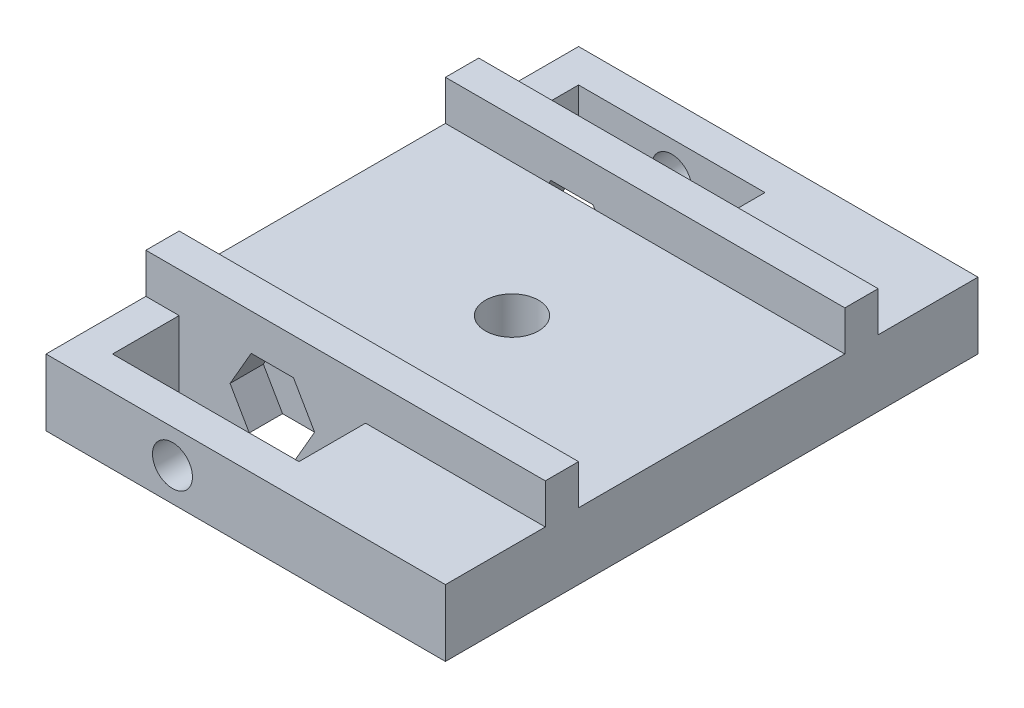
SolidWorks part; units mm, degrees
note: The reader was unsure of these and kept them because the rebuilt part matched: shared geometry of "Sketch1<3>", "Sketch4<3>".
ref_plane "Front" through (0, 0, 0) normal (0, 0, 1) x (1, 0, 0)
ref_plane "Top" through (0, 0, 0) normal (0, 1, 0) x (1, 0, 0)
ref_plane "Right" through (0, 0, 0) normal (1, 0, 0) x (0, 0, -1)
sketch "Sketch1" plane through (0, 0, 0) normal (0, 1, 0) x (1, 0, 0)
  line L0 (0, -20) -> (0, -22.5)
  line L1 (0, 0) -> (-30, 0)
  line L2 (0, 0) -> (0, -20)
  line L3 (0, -20) -> (-30, -20)
  line L4 (-30, 0) -> (-30, -20)
  line L5 (0, -22.5) -> (-30, -22.5)
  line L6 (-30, -22.5) -> (-30, -20)
  line L7 (0, 0) -> (-13.5, 0)
  line L8 (-30, 0) -> (0, 0)
  line L9 (-30, 0) -> (-30, 2.5)
  line L10 (-30, 2.5) -> (0, 2.5)
  line L11 (0, 0) -> (0, 2.5)
  line L12 (-30, 0) -> (-27.5, 0)
  line L13 (-30, 2.5) -> (-30, 7.5)
  line L14 (-30, 7.5) -> (0, 7.5)
  line L15 (0, 7.5) -> (0, 2.5)
  line L16 (0, 7.5) -> (0, 10)
  line L17 (0, 10) -> (-30, 10)
  line L18 (-30, 10) -> (-30, 7.5)
  line L19 (-13.5, 0) -> (-13.5, 10)
  line L20 (-27.5, 0) -> (-27.5, 10)
  dimension "D1" = 20
  dimension "D2" = 2.5
  dimension "D3" = 2.5
  dimension "D4" = 30
  dimension "D5" = 13.5
  dimension "D6" = 2.5
  dimension "D7" = 5
  dimension "D8" = 2.5
extrude "Boss-Extrude1" add sketch "Sketch1" along normal blind 5 contours L1 L8 L4 L3 L2 | L6 L5 L0 L3 | L20 L1 L19 L10 | L19 L1 L11 L10 | L19 L10 L15 L14 | L19 L14 L16 L17 | L20 L14 L19 L17 | L14 L20 L17 L18 | L10 L20 L14 L13 | L8 L20 L10 L9
extrude "Boss-Extrude2" add sketch "Sketch1<3>" along normal blind 8 contours L19 L1 L11 L10 | L20 L1 L19 L10 | L6 L5 L0 L3 | L8 L20 L10 L9
sketch "Sketch1<3>" plane through (0, 0, 0) normal (0, 1, 0) x (1, 0, 0) same geometry as "Sketch1"
sketch "Sketch3" plane through (0, 0, -10) normal (0, 0, -1) x (-1, 0, 0)
  line L0 (30, 2.5) -> (27.5, 2.5)
  line L1 (30, 5) -> (30, 0) construction
  line L2 (27.5, 2.5) -> (20.5, 2.5)
  circle A0 centre (20.5, 2.5) radius 1.5
  dimension "D1" = 2.5
  dimension "D2" = 7
extrude "Cut-Extrude2" cut sketch "Sketch3" against normal blind 2.5 contours A0
sketch "Sketch4" plane through (0, 0, -2.5) normal (0, 0, -1) x (-1, 0, 0)
  line L0 (27.5, 2.5) -> (20.5, 2.5)
  line L1 (27.5, 5) -> (27.5, 0) construction
  line L3 (23.6754, 2.5) -> (22.0877, 5.25)
  line L4 (22.0877, 5.25) -> (18.9123, 5.25)
  line L5 (18.9123, 5.25) -> (17.3246, 2.5)
  line L6 (17.3246, 2.5) -> (18.9123, -0.25)
  line L7 (18.9123, -0.25) -> (22.0877, -0.25)
  line L8 (22.0877, -0.25) -> (23.6754, 2.5)
  circle A0 centre (20.5, 2.5) radius 2.75 construction
  dimension "D1" = 7
extrude "Cut-Extrude3" cut sketch "Sketch4" against normal blind 2.5
ref_plane "Plane1" through (0, 0, 10) normal (0, 0, -1) x (-1, 0, 0)
mirror "Mirror1" about plane through (0, 0, 10) normal (0, 0, -1) of "Cut-Extrude2", "Cut-Extrude3", "Boss-Extrude1"
sketch "Sketch2" plane through (0, 5, 0) normal (0, 1, 0) x (1, 0, 0)
  line L0 (-30, -10) -> (0, -10)
  line L1 (-30, 0) -> (-30, -20) construction
  line L2 (0, 0) -> (0, -20) construction
  circle A0 centre (-15, -10) radius 2
extrude "Cut-Extrude1" cut sketch "Sketch2" against normal through all contours L0 A0 | L0 A0
extrude "Cut-Extrude4" cut sketch "Sketch4<3>" against normal blind 2.5
sketch "Sketch4<3>" plane through (0, 0, -2.5) normal (0, 0, -1) x (-1, 0, 0) same geometry as "Sketch4"
